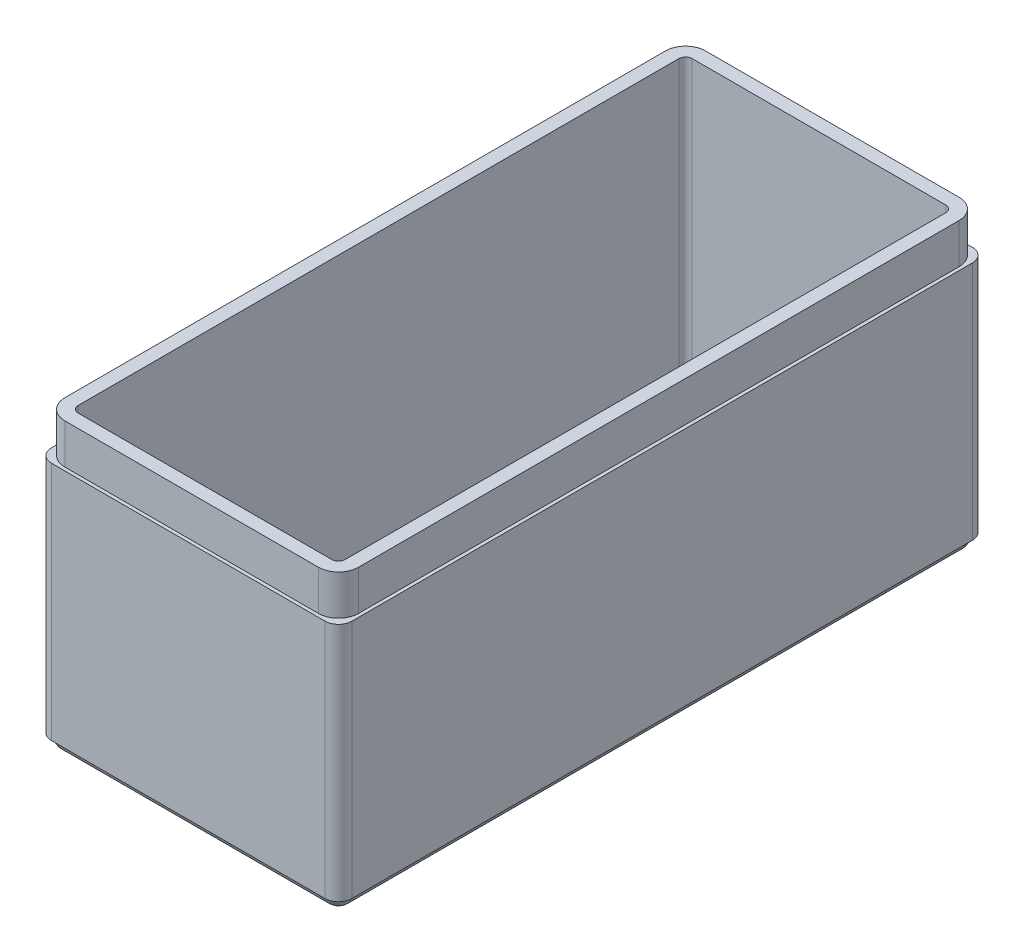
SolidWorks part; units mm, degrees
material "ABS"
ref_plane "Front Plane" through (0, 0, 0) normal (0, 0, 1) x (1, 0, 0)
ref_plane "Top Plane" through (0, 0, 0) normal (0, 1, 0) x (1, 0, 0)
ref_plane "Right Plane" through (0, 0, 0) normal (1, 0, 0) x (0, 0, -1)
sketch "Sketch1" plane through (0, 0, 0) normal (0, 1, 0) x (1, 0, 0)
  line L1 (-22.5, 48.5) -> (22.5, 48.5)
  line L2 (-22.5, 48.5) -> (-22.5, -48.5)
  line L3 (-22.5, -48.5) -> (22.5, -48.5)
  line L4 (22.5, 48.5) -> (22.5, -48.5)
  line L5 (-22.5, 48.5) -> (22.5, -48.5) construction
  line L6 (-22.5, -48.5) -> (22.5, 48.5) construction
  point P0 (0, 0)
  dimension "D1" = 45
  dimension "D2" = 97
extrude "Boss-Extrude1" add sketch "Sketch1" along normal mid plane 38
sketch "Sketch2" plane through (0, 19, 0) normal (0, 1, 0) x (1, 0, 0)
  line L0 (-22.5, -48.5) -> (22.5, -48.5) construction
  line L1 (-22, 48) -> (22, 48)
  line L2 (-22, 48) -> (-22, -48)
  line L3 (-22, -48) -> (22, -48)
  line L4 (22, 48) -> (22, -48)
  line L5 (-22, 48) -> (22, -48) construction
  line L6 (-22, -48) -> (22, 48) construction
  line L7 (-22.5, 48.5) -> (-22.5, -48.5) construction
  point P0 (0, 0)
  dimension "D1" = 0.5
  dimension "D2" = 0.5
extrude "Boss-Extrude2" add sketch "Sketch2" along normal blind 6
sketch "Sketch3" plane through (0, -19, 0) normal (0, -1, 0) x (1, 0, 0)
  line L1 (-22, 48) -> (22, 48)
  line L2 (-22, 48) -> (-22, -48)
  line L3 (-22, -48) -> (22, -48)
  line L4 (22.5, -48.5) -> (22.5, 48.5)
  line L5 (22.5, 48.5) -> (-22.5, 48.5)
  line L6 (-22.5, 48.5) -> (-22.5, -48.5)
  line L7 (-22.5, -48.5) -> (22.5, -48.5)
  line L8 (22.5, -48.5) -> (22.5, 48.5)
  line L9 (22.5, 48.5) -> (-22.5, 48.5)
  line L10 (-22.5, 48.5) -> (-22.5, -48.5)
  line L11 (-22.5, -48.5) -> (22.5, -48.5)
  line L12 (22, 48) -> (22, -48)
  line L13 (-22, 48) -> (22, -48) construction
  line L14 (-22, -48) -> (22, 48) construction
  point P2 (0, 0)
  dimension "D2" = 0.5
  dimension "D3" = 0.5
  dimension "D4" = 44
  dimension "D5" = 96
  dimension "D1" = 0
extrude "Cut-Extrude1" cut sketch "Sketch3" against normal blind 2
fillet "Fillet1" radius 2 4 edges at (0, -19, -48) (-22, -19, 0) (0, -19, 48) (22, -19, 0)
fillet "Fillet4" radius 3 4 edges at (-22, 22, 48) (22, 22, 48) (22, 22, -48) (-22, 22, -48)
fillet "Fillet5" radius 2 4 edges at (-22.5, 1, 48.5) (22.5, 1, 48.5) (-22.5, 1, -48.5) (22.5, 1, -48.5)
shell "Shell2" thickness 2 removed face at (0, 25, 0)
sketch "Sketch4" plane through (0, 17, 0) normal (0, -1, 0) x (1, 0, 0)
  line L4 (-20.5, 46.5) -> (-20.5, -46.5)
  line L5 (-20.5, -46.5) -> (20.5, -46.5)
  line L6 (20.5, -46.5) -> (20.5, 46.5)
  line L7 (20.5, 46.5) -> (-20.5, 46.5)
  line L8 (-20.5, 46.5) -> (-20.5, -46.5)
  line L9 (-20.5, -46.5) -> (20.5, -46.5)
  line L10 (20.5, -46.5) -> (20.5, 46.5)
  line L11 (20.5, 46.5) -> (-20.5, 46.5)
  line L12 (19, -46) -> (-19, -46) construction
  line L13 (-20, -45) -> (-20, 45) construction
  line L14 (-19, 46) -> (19, 46) construction
  line L15 (20, 45) -> (20, -45) construction
  line L16 (19, -46) -> (-19, -46)
  line L17 (-20, -45) -> (-20, 45)
  line L18 (-19, 46) -> (19, 46)
  line L19 (20, 45) -> (20, -45)
  arc A0 (19, -46) -> (20, -45) centre (19, -45) ccw construction
  arc A1 (-20, -45) -> (-19, -46) centre (-19, -45) ccw construction
  arc A2 (-19, 46) -> (-20, 45) centre (-19, 45) ccw construction
  arc A3 (20, 45) -> (19, 46) centre (19, 45) ccw construction
  arc A4 (19, -46) -> (20, -45) centre (19, -45) ccw
  arc A5 (-20, -45) -> (-19, -46) centre (-19, -45) ccw
  arc A6 (-19, 46) -> (-20, 45) centre (-19, 45) ccw
  arc A7 (20, 45) -> (19, 46) centre (19, 45) ccw
  dimension "D1" = 0
extrude "Boss-Extrude3" add sketch "Sketch4" along normal up to surface (34 mm away) up to face at (0, -17, 0)
